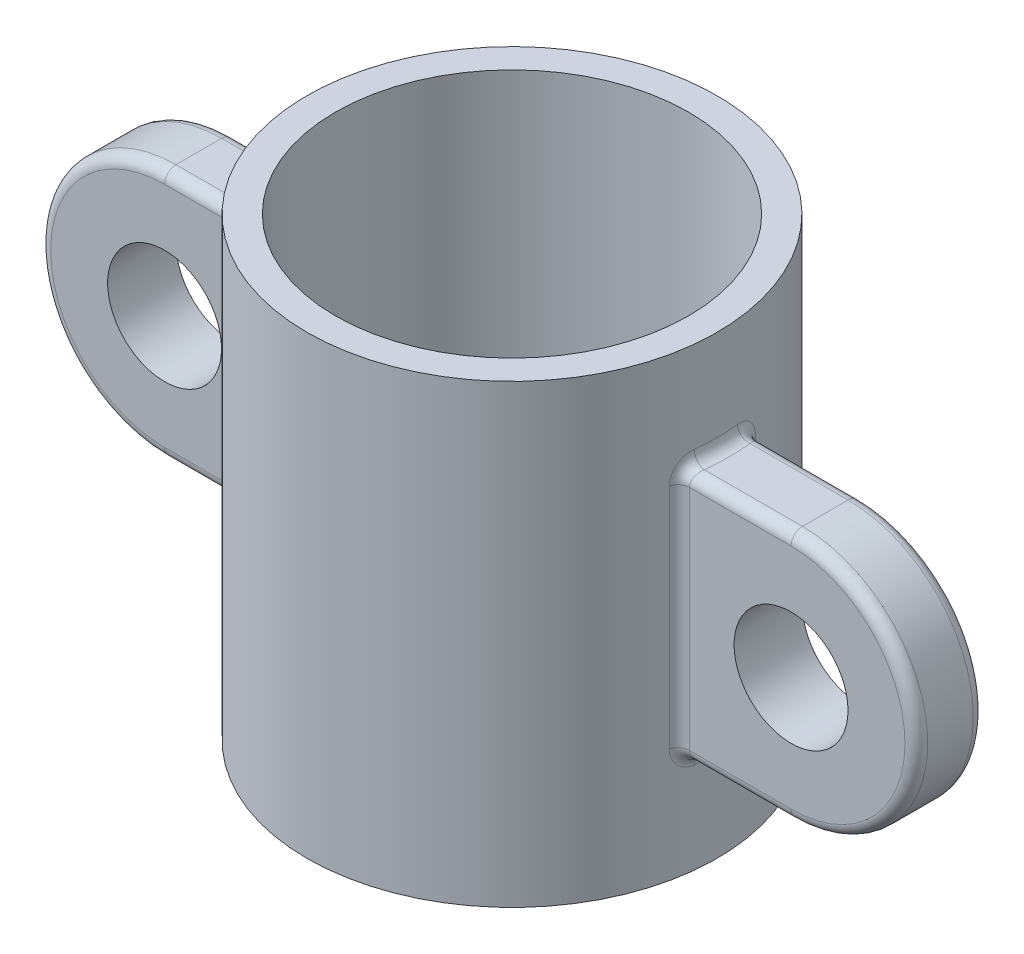
SolidWorks part; units mm, degrees
note: The reader was unsure of these and kept them because the rebuilt part matched: shared geometry of "Sketch1<3>".
ref_plane "Front Plane" through (0, 0, 0) normal (0, 0, 1) x (1, 0, 0)
ref_plane "Top Plane" through (0, 0, 0) normal (0, 1, 0) x (1, 0, 0)
ref_plane "Right Plane" through (0, 0, 0) normal (1, 0, 0) x (0, 0, -1)
sketch "Sketch1" plane through (0, 0, 0) normal (0, 1, 0) x (1, 0, 0)
  line L0 (-77.8592, 0) -> (74.7149, 0) construction
  line L1 (-77, 6) -> (-35.4965, 6)
  line L2 (77, 6) -> (77, -6)
  line L3 (77, -6) -> (35.4965, -6)
  line L4 (-77, -6) -> (-77, 6)
  line L5 (-35.4965, -6) -> (-77, -6)
  line L6 (35.4965, 6) -> (77, 6)
  circle A0 centre (0, 0) radius 36
  circle A1 centre (0, 0) radius 31
  point P10 (-77.8592, 0)
  dimension "D1" = 62
  dimension "D2" = 72
  dimension "D3" = 12
  dimension "D4" = 154
  dimension "D5" = 77
extrude "Boss-Extrude1" add sketch "Sketch1" along normal mid plane 80 contours L0 A0 A1 | A0 L0 A1
extrude "Boss-Extrude2" add sketch "Sketch1<3>" along normal mid plane 44
sketch "Sketch1<3>" plane through (0, 0, 0) normal (0, 1, 0) x (1, 0, 0) same geometry as "Sketch1"
sketch "Sketch2" plane through (0, 0, 6) normal (0, 0, 1) x (1, 0, 0)
  line L0 (0, -2.7705) -> (0, 8.3116) construction
  line L1 (-35.4965, -22) -> (-77, -22) construction
  line L2 (-77, 22) -> (-77, -22) construction
  line L6 (55, 22) -> (84.9007, 22)
  line L7 (84.9007, 22) -> (84.9007, -22)
  line L8 (84.9007, -22) -> (55, -22)
  circle A0 centre (-55, 0) radius 10
  circle A1 centre (-55, 0) radius 22
  arc A4 (55, 22) -> (55, -22) centre (55, 0) cw
  circle A5 centre (55, 0) radius 10
  line M9 (-77, -22) -> (-35.4965, -22)
  line M11 (-35.4965, 22) -> (-77, 22)
  line M12 (-77, 22) -> (-77, -22)
  dimension "D1" = 20
extrude "Cut-Extrude1" cut sketch "Sketch2" against normal up to next contours A1 M11 M12 | A1 M12 M9 | A0 | A5 | L8 A4 L6 L7
fillet "Fillet1" radius 2 20 edges at (36, -22, 0) (35.4965, 0, -6) (35.4965, 0, 6) (45.2482, 22, -6) (45.2482, -22, -6) (45.2482, -22, 6) (77, 0, 6) (-45.2482, 22, 6) (-77, 0, 6) (-45.2482, 22, -6) (-77, 0, -6) (36, 22, 0) (77, 0, -6) (45.2482, 22, 6) (-45.2482, -22, 6) (-45.2482, -22, -6) (-35.4965, 0, -6) (-36, -22, 0) (-36, 22, 0) (-35.4965, 0, 6)
